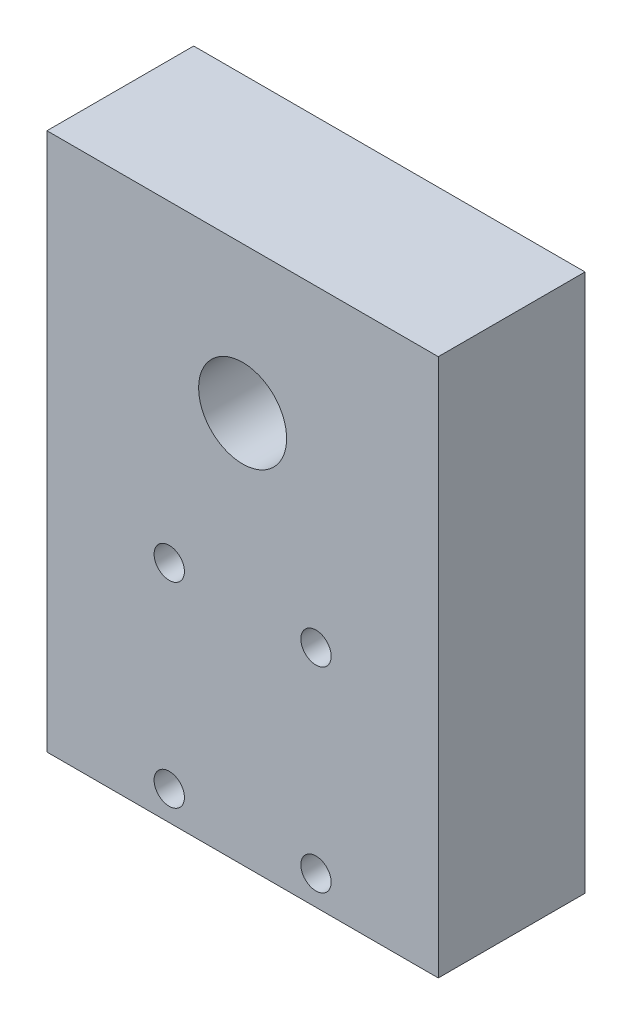
SolidWorks part; units mm, degrees
ref_plane "Front" through (0, 0, 0) normal (0, 0, 1) x (1, 0, 0)
ref_plane "Top" through (0, 0, 0) normal (0, 1, 0) x (1, 0, 0)
ref_plane "Right" through (0, 0, 0) normal (1, 0, 0) x (0, 0, -1)
sketch "Esquisse1" plane through (0, 0, 0) normal (0, 0, 1) x (1, 0, 0)
  line L1 (0, 0) -> (40, 0)
  line L2 (0, 0) -> (0, 30)
  line L3 (0, 30) -> (40, 30)
  line L4 (40, 0) -> (40, 30)
  dimension "D1" = 40
  dimension "D2" = 30
extrude "Boss.-Extru.1" add sketch "Esquisse1" along normal blind 15
sketch "Esquisse2" plane through (0, 0, 15) normal (0, 0, 1) x (1, 0, 0)
  line L0 (20, 15) -> (20, 0) construction
  line L1 (0, 0) -> (40, 0) construction
  line L2 (0, 15) -> (20, 15) construction
  line L3 (0, 30) -> (0, 0) construction
  circle A0 centre (20, 15) radius 11
  dimension "D1" = 22
extrude "Enlèv. mat.-Extru.1" cut sketch "Esquisse2" along normal blind 7 from vertex starting at point (40, 30, 0)
sketch "Esquisse3" plane through (0, 0, 15) normal (0, 0, 1) x (1, 0, 0)
  line L0 (40, 0) -> (40, 30) construction
  line L1 (0, 0) -> (40, 0)
  line L2 (0, 0) -> (0, -25)
  line L3 (0, -25) -> (40, -25)
  line L4 (40, 0) -> (40, -25)
  dimension "D1" = 25
extrude "Boss.-Extru.2" add sketch "Esquisse3" against normal up to vertex (15 mm away) up to point (40, 0, 0)
sketch "Esquisse4" plane through (0, 0, 15) normal (0, 0, 1) x (1, 0, 0)
  line L0 (20, -25) -> (20, 1) construction
  line L1 (0, -25) -> (40, -25) construction
  line L2 (20, -12) -> (30.0882, -12) construction
  circle A0 centre (27.5, -22) radius 1.55
  circle A1 centre (27.5, -2) radius 1.55
  circle A2 centre (12.5, -2) radius 1.55
  circle A3 centre (12.5, -22) radius 1.55
  dimension "D1" = 20
  dimension "D2" = 15
  dimension "D3" = 3.1
  dimension "D4" = 26
extrude "Enlèv. mat.-Extru.2" cut sketch "Esquisse4" against normal up to vertex (15 mm away) up to point (40, 30, 0)
sketch "Esquisse9" plane through (0, 0, 7) normal (0, 0, -1) x (-1, 0, 0)
  circle A0 centre (-20, 15) radius 10
  dimension "D1" = 20
extrude "Enlèv. mat.-Extru.5" cut sketch "Esquisse9" against normal blind 1
sketch "Esquisse10" plane through (0, 0, 8) normal (0, 0, -1) x (-1, 0, 0)
  circle A0 centre (-20, 15) radius 4.5
  dimension "D1" = 9
extrude "Enlèv. mat.-Extru.6" cut sketch "Esquisse10" against normal through all
